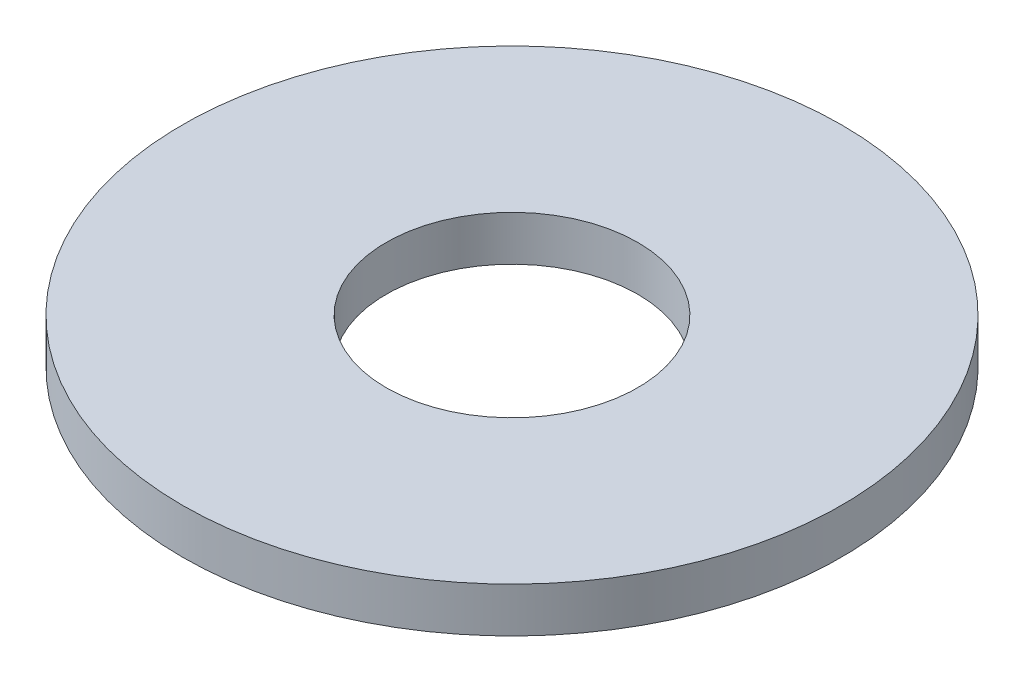
SolidWorks part; units mm, degrees
ref_plane "Plan1" through (0, 0, 0) normal (0, 0, 1) x (1, 0, 0)
ref_plane "Plan2" through (0, 0, 0) normal (0, 1, 0) x (1, 0, 0)
ref_plane "Plan3" through (0, 0, 0) normal (1, 0, 0) x (0, 0, -1)
ref_axis "Axe" through (0, 12.8848, 0) along (0, -1, 0)
sketch "Esquisse1" plane through (0, 0, 0) normal (0, 0, 1) x (1, 0, 0)
  line L1 (0, 0) -> (0, 2.5443) construction
  line L2 (4.2, 0) -> (4.2, 1.5)
  line L3 (4.2, 0) -> (11, 0)
  line L4 (11, 0) -> (11, 1.5)
  line L5 (11, 1.5) -> (4.2, 1.5)
  line L6 (4.2, 0) -> (-4.2, 0) construction
  line L7 (11, 0) -> (-11, 0) construction
  dimension "Epaisseur" = 1.5
  dimension "Rint" = 4.2
  dimension "Rext" = 11
  dimension "Diamètre de passage" = 8.4
  dimension "Diamètre extérieur" = 22
revolve "Base" add sketch "Esquisse1" angle 360 about L1
equation "\"Rext@Esquisse1\"=\"Diamètre extérieur@Esquisse1\"/2"
equation "\"Rint@Esquisse1\" = \"Diamètre de passage@Esquisse1\"/2"
